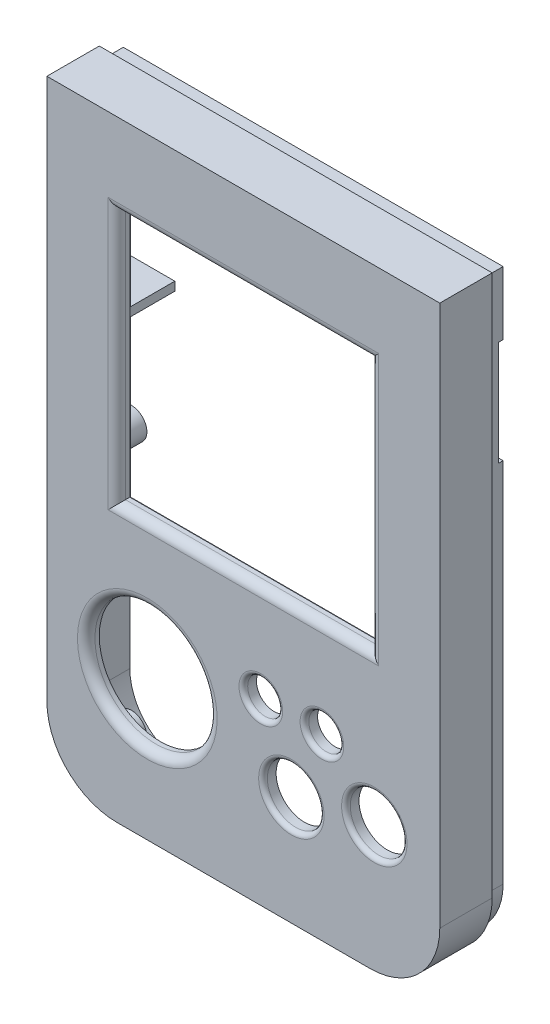
SolidWorks part; units mm, degrees
ref_plane "前视基准面" through (0, 0, 0) normal (0, 0, 1) x (1, 0, 0)
ref_plane "上视基准面" through (0, 0, 0) normal (0, 1, 0) x (1, 0, 0)
ref_plane "右视基准面" through (0, 0, 0) normal (1, 0, 0) x (0, 0, -1)
sketch "草图1" plane through (0, 0, 0) normal (0, 0, 1) x (1, 0, 0)
  line L1 (-45, 70) -> (0, 70)
  line L2 (-45, 70) -> (-45, 8)
  line L3 (-37, 0) -> (-8, 0)
  line L4 (0, 70) -> (0, 8)
  arc A2 (-37, 0) -> (-45, 8) centre (-37, 8) cw
  arc A3 (-8, 0) -> (0, 8) centre (-8, 8) ccw
  point P7 (0, 70)
  point P9 (-45, 0)
  point P10 (-45, 70)
  point P13 (0, 0)
  dimension "D3" = 8
  dimension "D1" = 45
  dimension "D2" = 70
extrude "凸台-拉伸1" add sketch "草图1" along normal blind 8 contours L1 L4 A3 L3 A2 L2
shell "抽壳2" thickness 1.5 removed face at (-22.5, 25.4477, 0)
sketch "草图4" plane through (0, 0, 0) normal (0, 0, -1) x (-1, 0, 0)
  line L0 (22.5, 68.5) -> (22.5, 50068.5) construction
  line L1 (8, 60.5) -> (37, 60.5)
  line L2 (8, 60.5) -> (8, 31.5)
  line L3 (8, 31.5) -> (37, 31.5)
  line L4 (37, 60.5) -> (37, 31.5)
  line L5 (43.5, 68.5) -> (1.5, 68.5) construction
  line L6 (45, 70) -> (0, 70) construction
  line L7 (45, 70) -> (45, 8) construction
  line L8 (0, 70) -> (0, 8) construction
  circle A0 centre (33.5, 16) radius 7
  circle A1 centre (7.5, 14.5) radius 3.25
  circle A2 centre (17, 12.5) radius 3.25
  circle A3 centre (13.5, 20.5) radius 2
  circle A4 centre (20.5, 20.5) radius 2
  point P8 (22.5, 68.5)
  dimension "D4" = 14
  dimension "D7" = 6.5
  dimension "D8" = 6.5
  dimension "D13" = 4
  dimension "D14" = 4
  dimension "D1" = 29
  dimension "D2" = 29
  dimension "D3" = 9.5
  dimension "D5" = 11.5
  dimension "D6" = 54
  dimension "D9" = 7.5
  dimension "D10" = 17
  dimension "D11" = 2
  dimension "D12" = 3.5
  dimension "D15" = 8
  dimension "D16" = 7
  dimension "D17" = 13.5
extrude "切除-拉伸3" cut sketch "草图4" against normal through all
fillet "圆角1" radius 1 4 edges at (-22.5, 60.5, 8) (-8, 46, 8) (-22.5, 31.5, 8) (-37, 46, 8)
fillet "圆角2" radius 1 1 edges at (-40.5, 16, 8)
fillet "圆角3" radius 0.5 4 edges at (-15.5, 20.5, 8) (-22.5, 20.5, 8) (-10.75, 14.5, 8) (-20.25, 12.5, 8)
sketch "草图5" plane through (0, 0, 6.5) normal (0, 0, -1) x (-1, 0, 0)
  line L1 (6.65, 65.75) -> (38.35, 65.75)
  line L2 (6.65, 65.75) -> (6.65, 30.15)
  line L3 (6.65, 30.15) -> (38.35, 30.15)
  line L4 (38.35, 65.75) -> (38.35, 30.15)
  line L6 (22.5, 55.8413) -> (22.5, 50055.8413) construction
  line L7 (8, 31.5) -> (8, 60.5) construction
  line L8 (37, 60.5) -> (37, 31.5) construction
  line L9 (37, 31.5) -> (8, 31.5) construction
  line L10 (39.35, 66.75) -> (39.35, 29.15)
  line L11 (5.65, 29.15) -> (39.35, 29.15)
  line L12 (5.65, 66.75) -> (5.65, 29.15)
  line L13 (5.65, 66.75) -> (39.35, 66.75)
  dimension "D1" = 31.7
  dimension "D2" = 35.6
  dimension "D3" = 1.35
  dimension "D4" = 1
extrude "凸台-拉伸2" add sketch "草图5" along normal blind 1.4
sketch "草图6" plane through (0, 0, 6.5) normal (0, 0, -1) x (-1, 0, 0)
  line L0 (45, 70) -> (0, 70) construction
  line L1 (0, 70) -> (0, 8) construction
  line L2 (4.5, 65.5) -> (4.5, 35.25) construction
  line L3 (22.5, -955.0295) -> (22.5, 49044.9705) construction
  line L4 (45, 70) -> (45, 8) construction
  circle A0 centre (4.5, 65.5) radius 1.75
  circle A1 centre (4.5, 65.5) radius 0.75
  circle A2 centre (4.5, 35.25) radius 1.75
  circle A3 centre (4.5, 35.25) radius 0.75
  circle A4 centre (4.5, 5) radius 1.75
  circle A5 centre (4.5, 5) radius 0.75
  circle A6 centre (40.5, 5) radius 0.75
  circle A7 centre (40.5, 5) radius 1.75
  circle A8 centre (40.5, 35.25) radius 0.75
  circle A9 centre (40.5, 35.25) radius 1.75
  circle A10 centre (40.5, 65.5) radius 0.75
  circle A11 centre (40.5, 65.5) radius 1.75
  dimension "D1" = 3.5
  dimension "D4" = 1
  dimension "D2" = 4.5
  dimension "D3" = 4.5
  dimension "D6" = 30.25
  dimension "D5" = 3
extrude "凸台-拉伸3" add sketch "草图6" along normal blind 3.7
sketch "草图7" plane through (0, 0, 0) normal (0, 0, -1) x (-1, 0, 0)
  line L0 (45, 70) -> (45, 8) construction
  line L1 (0, 70) -> (45, 70)
  line L2 (0, 70) -> (0, 8)
  line L3 (8, 0) -> (37, 0)
  line L4 (45, 70) -> (45, 8)
  line L5 (37, 0) -> (8, 0) construction
  line L6 (0.75, 69.25) -> (44.25, 69.25)
  line L7 (44.25, 69.25) -> (44.25, 8)
  line L8 (8, 0.75) -> (37, 0.75)
  line L9 (0.75, 69.25) -> (0.75, 8)
  arc A0 (37, 0) -> (45, 8) centre (37, 8) ccw
  arc A1 (0, 8) -> (8, 0) centre (8, 8) ccw
  arc A2 (37, 0.75) -> (44.25, 8) centre (37, 8) ccw
  arc A3 (0.75, 8) -> (8, 0.75) centre (8, 8) ccw
  dimension "D1" = 8
  dimension "D2" = 0.75
extrude "切除-拉伸4" cut sketch "草图7" against normal blind 2
sketch "草图8" plane through (0, 0, 0) normal (0, 0, -1) x (-1, 0, 0)
  line L0 (0.75, 69.25) -> (0.75, 8) construction
  line L1 (0.75, 62) -> (1.5, 62)
  line L2 (0.75, 62) -> (0.75, 50)
  line L3 (0.75, 50) -> (1.5, 50)
  line L4 (1.5, 62) -> (1.5, 50)
  line L5 (1.5, 68.5) -> (1.5, 8) construction
  line L6 (45, 70) -> (0, 70) construction
  dimension "D1" = 8
  dimension "D2" = 12
extrude "切除-拉伸5" cut sketch "草图8" against normal blind 0.5
sketch "草图9" plane through (0, 0, 6.5) normal (0, 0, -1) x (-1, 0, 0)
  line L0 (43.5, 68.5) -> (43.5, 8) construction
  line L1 (43.5, 49) -> (38.35, 49)
  line L2 (43.5, 49) -> (43.5, 48)
  line L3 (43.5, 48) -> (38.35, 48)
  line L4 (38.35, 49) -> (38.35, 48)
  line L5 (38.35, 30.15) -> (38.35, 65.75) construction
  line L6 (45, 70) -> (0, 70) construction
  dimension "D1" = 21
  dimension "D2" = 1
extrude "凸台-拉伸4" add sketch "草图9" along normal blind 6.5
